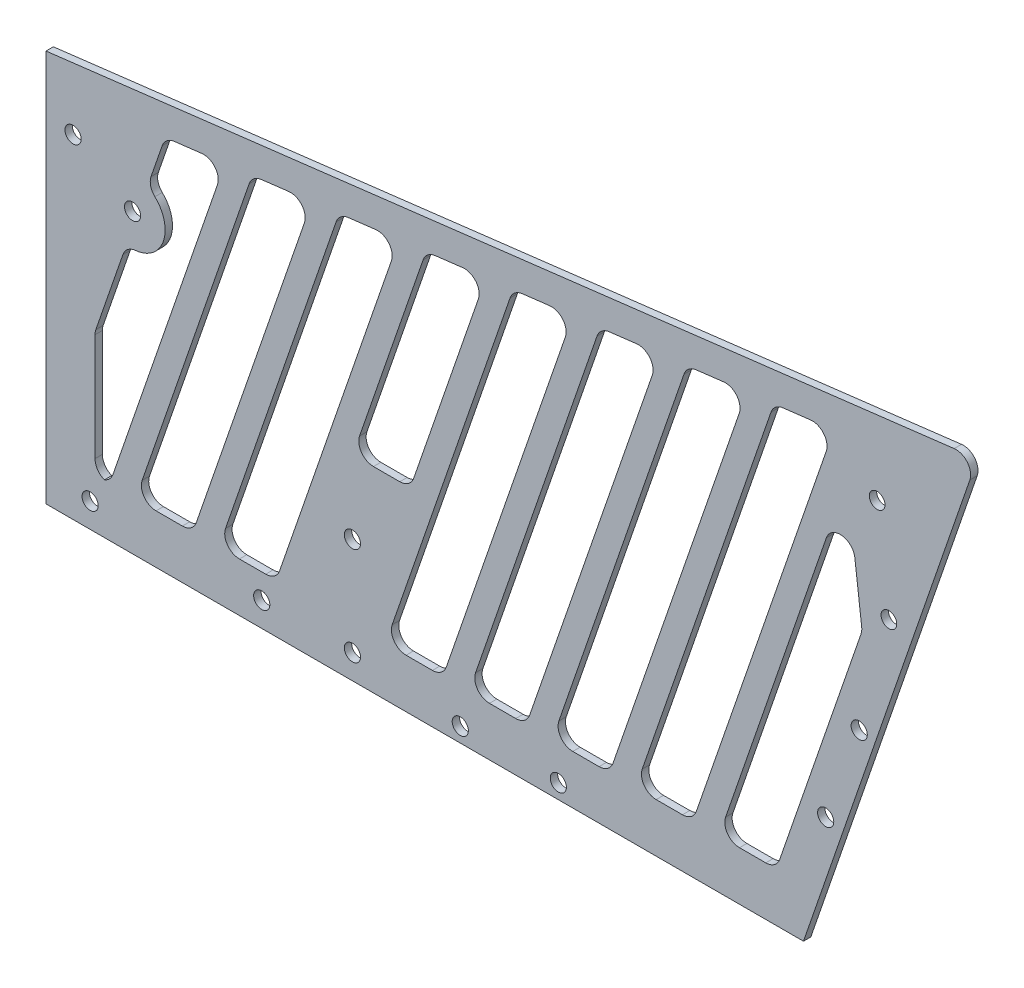
SolidWorks part; units mm, degrees
other "标注1"
sketch "草图8" plane through (190, 0, 1.5) normal (0.4662, -0.1687, 0.8685) x (0.883, 0.0286, -0.4684)
material "自定义塑料"
ref_plane "前视基准面" through (0, 0, 0) normal (0, 0, 1) x (1, 0, 0)
ref_plane "上视基准面" through (0, 0, 0) normal (0, 1, 0) x (1, 0, 0)
ref_plane "右视基准面" through (0, 0, 0) normal (1, 0, 0) x (0, 0, -1)
sketch "草图1" plane through (0, 0, 0) normal (0, 0, 1) x (1, 0, 0)
  line L0 (44, 5) -> (9, 5) construction
  line L1 (0, 0) -> (49, 0)
  line L2 (0, 0) -> (0, 80)
  line L5 (49, 0) -> (154.5, 0)
  line L6 (154.5, 0) -> (190, 102.9694)
  line L7 (0, 80) -> (190, 102.9694)
  circle A0 centre (44, 5) radius 1.65
  circle A1 centre (9, 5) radius 1.65
  circle A2 centre (62.5, 5) radius 1.65
  circle A3 centre (62.5, 25) radius 1.65
  circle A4 centre (84.5, 3) radius 1.65
  circle A5 centre (104.5, 3) radius 1.65
  circle A6 centre (159.0292, 24.1724) radius 1.65
  circle A7 centre (165.8696, 42.9663) radius 1.65
  circle A8 centre (5.5167, 68) radius 1.65
  point P9 (173.819, 56.0356)
  dimension "D3" = 3.3
  dimension "D4" = 190
  dimension "D1" = 49
  dimension "D2" = 80
  dimension "D5" = 5
  dimension "D6" = 35
  dimension "D7" = 105.5
extrude "凸台-拉伸1" add sketch "草图1" along normal blind 1.5
sketch "草图2" plane through (0, 0, 0) normal (0, 0, -1) x (-1, 0, 0)
  circle A0 centre (-17.6548, 60.5226) radius 1.65
  dimension "D1" = 3.3
  dimension "D2" = 60.5226
  dimension "D3" = 17.6548
extrude "切除-拉伸1" cut sketch "草图2" against normal through all
sketch "草图5" plane through (0, 0, 1.5) normal (0, 0, 1) x (1, 0, 0)
  line L0 (0, 80) -> (0, 0) construction
  line L1 (0, 0) -> (154.5, 0) construction
  circle A0 centre (169.5262, 85.385) radius 1.6
  circle A1 centre (171.9266, 65.5296) radius 1.6
  dimension "D1" = 3.2
  dimension "D2" = 169.5262
  dimension "D3" = 171.9266
  dimension "D4" = 65.5296
  dimension "D5" = 85.385
extrude "切除-拉伸3" cut sketch "草图5" against normal through all
sketch "草图6" plane through (0, 0, 0) normal (0, 0, -1) x (-1, 0, 0)
  line L0 (-154.5, 10) -> (0, 10)
  line L1 (-10, 0) -> (-10, 80)
  line L2 (-0.7201, 74.0434) -> (-181.2031, 95.8622)
  line L3 (-181.2031, 95.8622) -> (-148.8277, 1.9556)
  line L4 (0, 0) -> (0, 80)
  line L5 (-154.5, 0) -> (0, 0)
  line L6 (-190, 102.9694) -> (-154.5, 0)
  line L7 (0, 80) -> (-190, 102.9694)
  line L8 (0, 0) -> (0, 80)
  line L9 (-154.5, 0) -> (0, 0)
  line L10 (-190, 102.9694) -> (-154.5, 0)
  line L11 (0, 80) -> (-190, 102.9694)
  line L12 (-162.4894, 93.5999) -> (-167.1453, 55.0868)
  line L13 (-164.2031, 95.8622) -> (-131.8277, 1.9556)
  line L14 (-147.2031, 95.8622) -> (-114.8277, 1.9556)
  line L15 (-130.2031, 95.8622) -> (-97.8277, 1.9556)
  line L16 (-113.2031, 95.8622) -> (-80.8277, 1.9556)
  line L17 (-96.2031, 95.8622) -> (-63.8277, 1.9556)
  line L18 (-79.2031, 95.8622) -> (-46.8277, 1.9556)
  line L19 (-62.2031, 95.8622) -> (-29.8277, 1.9556)
  line L20 (-45.2031, 95.8622) -> (-12.8277, 1.9556)
  line L21 (-28.2031, 95.8622) -> (4.1723, 1.9556)
  line L22 (-166.5666, 95.0474) -> (-134.1912, 1.1408)
  line L23 (-149.5666, 95.0474) -> (-117.1912, 1.1408)
  line L24 (-132.5666, 95.0474) -> (-100.1912, 1.1408)
  line L25 (-115.5666, 95.0474) -> (-83.1912, 1.1408)
  line L26 (-98.5666, 95.0474) -> (-66.1912, 1.1408)
  line L27 (-81.5666, 95.0474) -> (-49.1912, 1.1408)
  line L28 (-64.5666, 95.0474) -> (-32.1912, 1.1408)
  line L29 (-47.5666, 95.0474) -> (-15.1912, 1.1408)
  line L30 (-30.5666, 95.0474) -> (1.8088, 1.1408)
  line L31 (-161.8397, 96.6771) -> (-129.4642, 2.7705)
  line L32 (-144.8397, 96.6771) -> (-112.4642, 2.7705)
  line L33 (-127.8397, 96.6771) -> (-95.4642, 2.7705)
  line L34 (-110.8397, 96.6771) -> (-78.4642, 2.7705)
  line L35 (-93.8397, 96.6771) -> (-61.4642, 2.7705)
  line L36 (-76.8397, 96.6771) -> (-44.4642, 2.7705)
  line L37 (-59.8397, 96.6771) -> (-27.4642, 2.7705)
  line L38 (-42.8397, 96.6771) -> (-10.4642, 2.7705)
  line L39 (-25.8397, 96.6771) -> (6.5358, 2.7705)
  line L40 (-178.8397, 96.6771) -> (-146.4642, 2.7705)
  circle A0 centre (-169.5262, 85.385) radius 1.6 construction
  circle A1 centre (-171.9266, 65.5296) radius 1.6 construction
  circle A2 centre (-165.8696, 42.9663) radius 1.5 construction
  circle A3 centre (-159.0292, 24.1724) radius 1.5 construction
  circle A4 centre (-104.5, 3) radius 1.65 construction
  circle A5 centre (-84.5, 3) radius 1.65 construction
  circle A6 centre (-62.5, 5) radius 1.65 construction
  circle A7 centre (-44, 5) radius 1.65 construction
  circle A8 centre (-62.5, 25) radius 1.65 construction
  circle A9 centre (-9, 5) radius 1.65 construction
  circle A10 centre (-17.6548, 60.5226) radius 1.65 construction
  circle A11 centre (-5.5167, 68) radius 1.65 construction
  circle A12 centre (-169.5262, 85.385) radius 1.6
  circle A13 centre (-171.9266, 65.5296) radius 1.6
  circle A14 centre (-165.8696, 42.9663) radius 1.5
  circle A15 centre (-159.0292, 24.1724) radius 1.5
  circle A16 centre (-104.5, 3) radius 1.65
  circle A17 centre (-84.5, 3) radius 1.65
  circle A18 centre (-62.5, 5) radius 1.65
  circle A19 centre (-44, 5) radius 1.65
  circle A20 centre (-62.5, 25) radius 1.65
  circle A21 centre (-9, 5) radius 1.65
  circle A22 centre (-17.6548, 60.5226) radius 1.65
  circle A23 centre (-5.5167, 68) radius 1.65
  circle A24 centre (-17.6548, 60.5226) radius 6.65
  circle A25 centre (-62.5, 25) radius 6.65
  dimension "D5" = 6
  dimension "D1" = 0
  dimension "D2" = 10
  dimension "D3" = 10
  dimension "D4" = 6
  dimension "D7" = 2.5
  dimension "D8" = 2.5
  dimension "D9" = 5
  dimension "D10" = 2.5
  dimension "D6" = 10
extrude "切除-拉伸4" cut sketch "草图6" against normal blind 10 contours A24 L30 L2 L38 L0 L1 | L2 L37 L0 L29 | L2 L36 L0 L28 | A25 L27 L2 L35 | L2 L34 L0 L26 | L2 L33 L0 L25 | L2 L32 L0 L24 | L2 L31 L0 L23 | L22 L12 L3 L0 region at (153.7758, 42.0864, 0) region at (140.3654, 51.3238, 0) region at (122.9962, 50.2516, 0) region at (105.627, 49.1793, 0) region at (88.2579, 48.1071, 0) region at (74.454, 57.0811, 0) region at (20.6801, 46.912, 0) region at (53.5197, 45.9626, 0) region at (36.1506, 44.8904, 0)
fillet "圆角3" radius 3 37 edges at (89.747, 84.806, 0.75) (77.5264, 83.3286, 0.75) (69.2455, 10, 0.75) (80.9567, 10, 0.75) (107.4863, 86.9505, 0.75) (95.2658, 85.4731, 0.75) (18.2455, 10, 0.75) (29.9567, 10, 0.75) (54.2682, 80.5169, 0.75) (42.0477, 79.0395, 0.75) (35.2455, 10, 0.75) (46.9567, 10, 0.75) (72.0076, 82.6614, 0.75) (59.7871, 81.1841, 0.75) (120.2455, 10, 0.75) (131.9567, 10, 0.75) (160.7044, 93.3841, 0.75) (148.4839, 91.9067, 0.75) (16.4115, 53.9898, 0.75) (10, 35.3929, 0.75) (10, 10, 0.75) (12.9567, 10, 0.75) (36.5289, 78.3723, 0.75) (24.3084, 76.895, 0.75) (20.7016, 66.4335, 0.75) (103.2455, 10, 0.75) (114.9567, 10, 0.75) (142.965, 91.2396, 0.75) (130.7445, 89.7622, 0.75) (86.2455, 10, 0.75) (97.9567, 10, 0.75) (125.2257, 89.095, 0.75) (113.0051, 87.6177, 0.75) (163.4184, 85.9157, 0.75) (137.2455, 10, 0.75) (166.4588, 60.7657, 0.75) (148.9567, 10, 0.75)
fillet "圆角4" radius 5 1 edges at (69.1497, 25.0627, 0.75)
sketch "草图7" plane through (0, 0, 1.5) normal (0, 0, 1) x (1, 0, 0)
  line L1 (76.1407, 40) -> (59.1407, 40)
  line L2 (76.1407, 40) -> (76.1407, 30)
  line L3 (76.1407, 30) -> (59.1407, 30)
  line L4 (59.1407, 40) -> (59.1407, 30)
  line L6 (0, 0) -> (154.5, 0) construction
  line L7 (94.6538, 83.698) -> (70.6169, 13.9778) construction
  dimension "D1" = 40
  dimension "D2" = 17
  dimension "D3" = 10
extrude "凸台-拉伸2" add sketch "草图7" against normal up to surface (1.5 mm away) up to face at (88.1355, 48.0309, 0)
fillet "圆角5" radius 3 2 edges at (74.2996, 40, 0.75) (62.5884, 40, 0.75)
fillet "圆角6" radius 3 1 edges at (190, 102.9694, 0.75)
